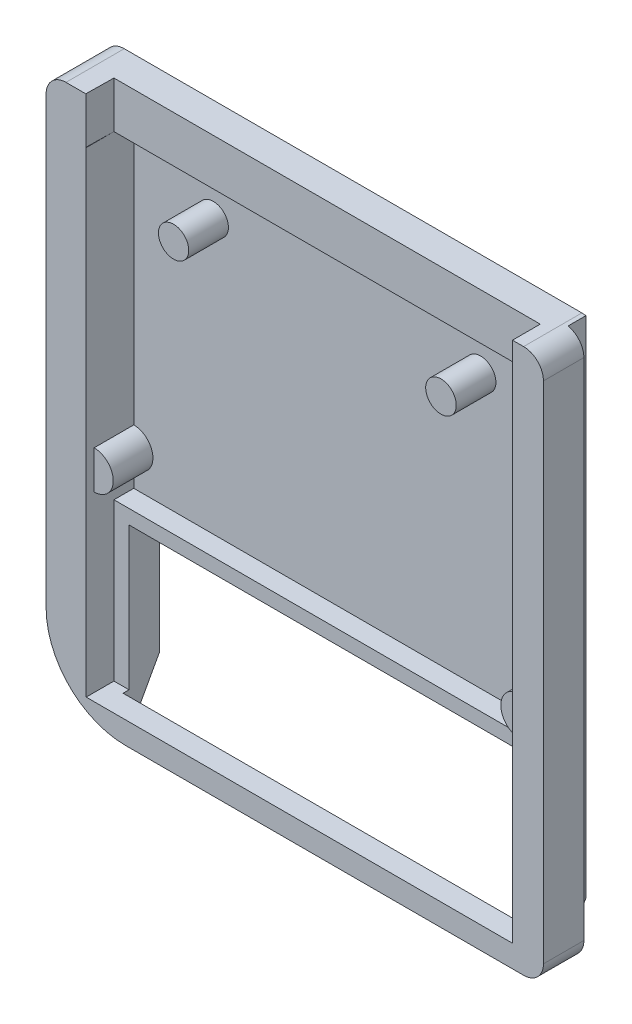
SolidWorks part; units mm, degrees
ref_plane "Front Plane" through (0, 0, 0) normal (0, 0, 1) x (1, 0, 0)
ref_plane "Top Plane" through (0, 0, 0) normal (0, 1, 0) x (1, 0, 0)
ref_plane "Right Plane" through (0, 0, 0) normal (1, 0, 0) x (0, 0, -1)
sketch "Sketch1" plane through (0, 0, -1.6) normal (0, 0, 1) x (1, 0, 0)
  circle A0 centre (121.275, -72.675) radius 0.9705
  circle A1 centre (138.4, -72.7) radius 0.9791
  circle A2 centre (138.4, -72.7) radius 1.0299 construction
  circle A3 centre (121.275, -72.675) radius 1.0213 construction
  circle A6 centre (138.4, -72.7) radius 1.0299 construction
  circle A7 centre (121.275, -72.675) radius 1.0213 construction
  dimension "D1" = 0.0508
extrude "Boss-Extrude1" add sketch "Sketch1" against normal blind 1.27 and the other way blind 1.27
sketch "Sketch3" plane through (0, 0, -2.87) normal (0, 0, 1) x (1, 0, 0)
  line L32 (143.4899, -89.1669) -> (143.49, -100.2279) construction
  line L33 (143.49, -100.2279) -> (116.18, -100.2279) construction
  line L34 (116.18, -100.2279) -> (116.185, -89.1027) construction
  line L36 (143.4899, -89.1669) -> (143.49, -100.2279)
  line L37 (143.49, -100.2279) -> (116.18, -100.2279)
  line L38 (116.18, -100.2279) -> (116.185, -89.1027)
  line L39 (117.1502, -100.2279) -> (117.1502, -91.0839)
  line L40 (117.1502, -91.0839) -> (143.4899, -91.0839)
  line L41 (116.1845, -90.1695) -> (143.4899, -90.1695)
  line L42 (118.6996, -101.6503) -> (144.2012, -101.6503)
  line L44 (144.2012, -66.7761) -> (114.8896, -66.7761)
  line L45 (113.6196, -68.0461) -> (113.6196, -96.5703)
  line L46 (116.185, -89.1027) -> (116.185, -69.7479)
  line L47 (116.185, -69.7479) -> (116.2, -40.2) construction
  line L48 (116.185, -69.7479) -> (143.49, -69.7479)
  line L49 (143.5, -40.2) -> (143.49, -69.7479) construction
  line L50 (143.49, -69.7479) -> (143.4899, -89.1669)
  line L51 (145.4712, -68.0461) -> (145.4712, -100.3803)
  arc A0 (118.6996, -101.6503) -> (113.6196, -96.5703) centre (118.6996, -96.5703) cw
  arc A1 (145.4712, -68.0461) -> (144.2012, -66.7761) centre (144.2012, -68.0461) ccw
  arc A2 (114.8896, -66.7761) -> (113.6196, -68.0461) centre (114.8896, -68.0461) ccw
  arc A3 (144.2012, -101.6503) -> (145.4712, -100.3803) centre (144.2012, -100.3803) ccw
  point P22 (113.6196, -101.6503)
  point P25 (145.4712, -66.7761)
  point P30 (145.4712, -101.6503)
  dimension "D8" = 5.08
  dimension "D9" = 1.27
  dimension "D2" = 34.8742
  dimension "D1" = 2.5654
  dimension "D3" = 31.8516
  dimension "D4" = 1.4224
  dimension "D5" = 3.5306
  dimension "D6" = 9.144
  dimension "D7" = 0.9144
sketch "Sketch4" plane through (0, 0, -2.87) normal (0, 0, 1) x (1, 0, 0)
  line L0 (113.6196, -68.0461) -> (113.6196, -96.5703) construction
  line L5 (118.6996, -101.6503) -> (144.2012, -101.6503) construction
  line L6 (145.4712, -68.0461) -> (145.4712, -100.3803) construction
  line L7 (144.2012, -66.7761) -> (114.8896, -66.7761) construction
  line L8 (113.6196, -68.0461) -> (113.6196, -96.5703)
  line L9 (118.6996, -101.6503) -> (144.2012, -101.6503)
  line L10 (145.4712, -68.0461) -> (145.4712, -100.3803)
  line L11 (144.2012, -66.7761) -> (114.8896, -66.7761)
  line L13 (117.1502, -91.0839) -> (143.49, -91.0839)
  line L14 (117.1502, -91.0839) -> (117.1502, -100.2279)
  line L15 (117.1502, -100.2279) -> (143.49, -100.2279)
  line L16 (143.49, -91.0839) -> (143.49, -100.2279)
  arc A0 (113.6196, -96.5703) -> (118.6996, -101.6503) centre (118.6996, -96.5703) ccw construction
  arc A1 (144.2012, -101.6503) -> (145.4712, -100.3803) centre (144.2012, -100.3803) ccw construction
  arc A2 (145.4712, -68.0461) -> (144.2012, -66.7761) centre (144.2012, -68.0461) ccw construction
  arc A3 (114.8896, -66.7761) -> (113.6196, -68.0461) centre (114.8896, -68.0461) ccw construction
  arc A4 (113.6196, -96.5703) -> (118.6996, -101.6503) centre (118.6996, -96.5703) ccw
  arc A5 (144.2012, -101.6503) -> (145.4712, -100.3803) centre (144.2012, -100.3803) ccw
  arc A6 (145.4712, -68.0461) -> (144.2012, -66.7761) centre (144.2012, -68.0461) ccw
  arc A7 (114.8896, -66.7761) -> (113.6196, -68.0461) centre (114.8896, -68.0461) ccw
extrude "Boss-Extrude2" add sketch "Sketch4" against normal blind 0.6858
sketch "Sketch7" plane through (0, 0, -2.87) normal (0, 0, 1) x (1, 0, 0)
  line L0 (113.6196, -68.0461) -> (113.6196, -96.5703) construction
  line L1 (116.185, -69.7479) -> (143.49, -69.7479)
  line L2 (116.185, -69.7479) -> (116.185, -100.2279)
  line L3 (116.185, -100.2279) -> (143.49, -100.2279)
  line L4 (143.49, -69.7479) -> (143.49, -100.2279)
  line L5 (118.6996, -101.6503) -> (144.2012, -101.6503) construction
  line L6 (145.4712, -68.0461) -> (145.4712, -100.3803) construction
  line L7 (144.2012, -66.7761) -> (114.8896, -66.7761) construction
  line L8 (113.6196, -68.0461) -> (113.6196, -96.5703)
  line L9 (118.6996, -101.6503) -> (144.2012, -101.6503)
  line L10 (145.4712, -68.0461) -> (145.4712, -100.3803)
  line L11 (144.2012, -66.7761) -> (114.8896, -66.7761)
  arc A0 (113.6196, -96.5703) -> (118.6996, -101.6503) centre (118.6996, -96.5703) ccw construction
  arc A1 (144.2012, -101.6503) -> (145.4712, -100.3803) centre (144.2012, -100.3803) ccw construction
  arc A2 (145.4712, -68.0461) -> (144.2012, -66.7761) centre (144.2012, -68.0461) ccw construction
  arc A3 (114.8896, -66.7761) -> (113.6196, -68.0461) centre (114.8896, -68.0461) ccw construction
  arc A4 (113.6196, -96.5703) -> (118.6996, -101.6503) centre (118.6996, -96.5703) ccw
  arc A5 (144.2012, -101.6503) -> (145.4712, -100.3803) centre (144.2012, -100.3803) ccw
  arc A6 (145.4712, -68.0461) -> (144.2012, -66.7761) centre (144.2012, -68.0461) ccw
  arc A7 (114.8896, -66.7761) -> (113.6196, -68.0461) centre (114.8896, -68.0461) ccw
extrude "Boss-Extrude10" add sketch "Sketch7" along normal blind 3.048
sketch "Sketch8" plane through (0, 0, -2.87) normal (0, 0, 1) x (1, 0, 0)
  line L0 (116.185, -89.1027) -> (116.185, -86.6528)
  line L1 (116.185, -89.1027) -> (116.185, -69.7479) construction
  line L2 (143.4899, -89.1669) -> (143.4899, -86.6528)
  line L3 (143.49, -69.7479) -> (143.4899, -89.1669) construction
  arc A0 (116.185, -86.6528) -> (116.185, -89.1027) centre (116.185, -87.8777) cw
  arc A1 (143.4899, -89.1669) -> (143.4899, -86.6528) centre (143.4899, -87.9098) cw
  line M1 (116.185, -69.7479) -> (116.185, -100.2279)
  dimension "D1" = 2.4499
extrude "Boss-Extrude11" add sketch "Sketch8" along normal blind 2.54 contours A0 M1 | A1 L2 region at (116.7049, -87.8777, -2.87) region at (142.9564, -87.9098, -2.87)
sketch "Sketch10" plane through (0, 0, -2.87) normal (0, 0, 1) x (1, 0, 0)
  line L0 (116.1845, -90.1695) -> (143.4899, -90.1695)
  line L1 (143.4899, -90.1695) -> (143.4899, -91.0839)
  line L2 (143.4899, -91.0839) -> (117.1502, -91.0839)
  line L3 (117.1502, -91.0839) -> (117.1502, -100.2279)
  line L4 (117.1502, -100.2279) -> (116.185, -100.2279)
  line L5 (116.185, -100.2279) -> (116.1845, -90.1695)
extrude "Boss-Extrude12" add sketch "Sketch10" along normal blind 1.27
sketch "Sketch11" plane through (145.4712, 0, 0) normal (1, 0, 0) x (0, 0, -1)
  line L0 (3.5558, -101.6503) -> (-0.178, -101.6503) construction
  line L1 (3.5558, -66.7761) -> (2.4128, -66.7761)
  line L2 (3.5558, -66.7761) -> (3.5558, -101.6503)
  line L3 (3.5558, -101.6503) -> (2.4128, -101.6503)
  line L4 (2.4128, -66.7761) -> (2.4128, -101.6503)
  line L5 (-0.178, -100.3803) -> (-0.178, -68.0461) construction
  dimension "D1" = 2.5908
extrude "Cut-Extrude2" cut sketch "Sketch11" against normal blind 1.016
sketch "Sketch12" plane through (0, -69.7479, 0) normal (0, -1, 0) x (1, 0, 0)
  line L0 (143.4899, -1.6) -> (116.185, -1.6) construction
  line L1 (143.4899, -1.6) -> (116.185, -1.6)
  line L2 (116.185, -1.6) -> (116.1596, 0.178)
  line L3 (118.6996, 0.178) -> (113.6196, 0.178) construction
  line L4 (116.1596, 0.178) -> (143.4899, 0.178)
  line L5 (118.6996, 0.178) -> (144.2012, 0.178) construction
  line L6 (143.4899, 0.178) -> (143.4899, -1.6)
extrude "Cut-Extrude3" cut sketch "Sketch12" against normal up to next (2.9718 mm away)
sketch "Sketch13" plane through (145.4712, 0, 0) normal (1, 0, 0) x (0, 0, -1)
  line L0 (3.5558, -101.6503) -> (2.1588, -101.6503)
  line L1 (3.5558, -101.6503) -> (-0.178, -101.6503) construction
  line L2 (2.1588, -101.6503) -> (3.5558, -99.1103)
  line L3 (3.5558, -66.8018) -> (3.5558, -101.6246) construction
  line L4 (3.5558, -99.1103) -> (3.5558, -101.6503)
  dimension "D1" = 2.54
  dimension "D2" = 1.397
extrude "Cut-Extrude4" cut sketch "Sketch13" against normal up to surface (31.8516 mm away) up to face at (113.6196, -82.3082, -1.6889)
sketch "Sketch14" plane through (113.6196, 0, 0) normal (-1, 0, 0) x (0, 0, 1)
  line L0 (-3.5558, -68.0461) -> (-3.5558, -96.5703) construction
  line L1 (-3.5558, -95.6559) -> (-1.473, -95.6559)
  line L2 (-3.5558, -95.6559) -> (-3.5558, -101.6503)
  line L3 (-3.5558, -101.6503) -> (-1.473, -101.6503)
  line L4 (-1.473, -95.6559) -> (-1.473, -101.6503)
  line L5 (-2.1588, -101.6503) -> (0.178, -101.6503) construction
  dimension "D1" = 2.0828
  dimension "D2" = 5.9944
extrude "Cut-Extrude5" cut sketch "Sketch14" against normal blind 1.397
sketch "Sketch15" plane through (113.6196, 0, 0) normal (-1, 0, 0) x (0, 0, 1)
  line L0 (-3.5558, -68.0461) -> (-3.5558, -95.6559) construction
  line L1 (-3.5558, -88.1629) -> (-1.7778, -88.1629)
  line L2 (-3.5558, -88.1629) -> (-3.5558, -85.3181)
  line L3 (-3.5558, -85.3181) -> (-1.7778, -85.3181)
  line L4 (-1.7778, -88.1629) -> (-1.7778, -85.3181)
  line L5 (-3.5558, -66.7761) -> (0.178, -66.7761) construction
  dimension "D1" = 18.542
  dimension "D2" = 1.778
  dimension "D3" = 2.8448
extrude "Cut-Extrude6" cut sketch "Sketch15" against normal blind 1.4986
sketch "Sketch16" plane through (0, -101.6503, 0) normal (0, -1, 0) x (1, 0, 0)
  line L0 (143.49, -3.5558) -> (143.49, -2.9411) construction
  line L1 (117.1502, -3.5558) -> (143.49, -3.5558)
  line L2 (117.1502, -3.5558) -> (117.1502, -1.219)
  line L3 (117.1502, -1.219) -> (143.49, -1.219)
  line L4 (143.49, -3.5558) -> (143.49, -1.219)
  line L5 (118.6996, 0.178) -> (144.2012, 0.178) construction
  dimension "D1" = 1.397
extrude "Cut-Extrude7" cut sketch "Sketch16" against normal blind 3.81
